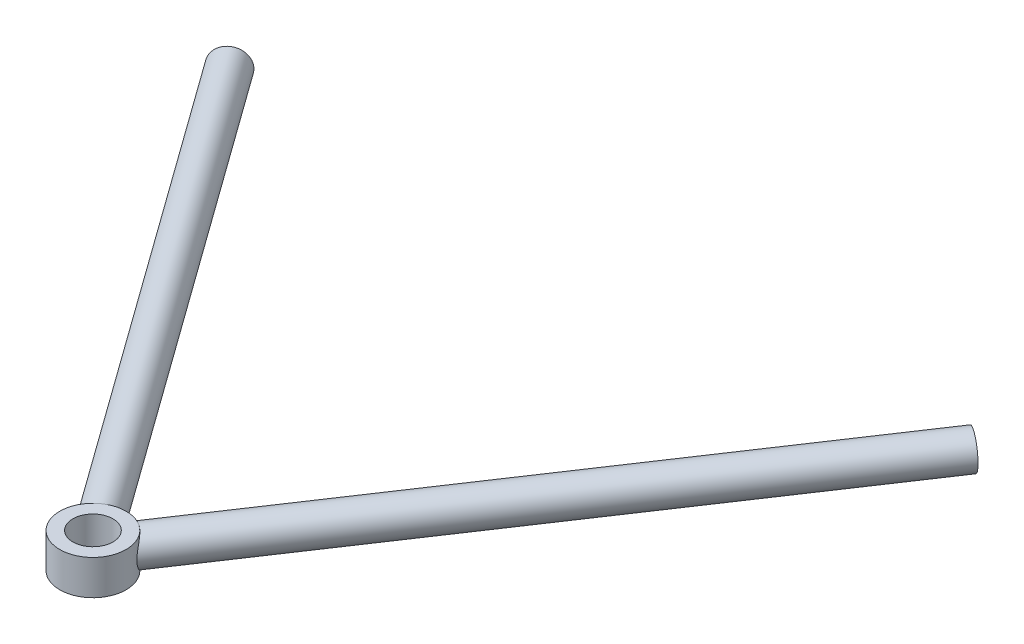
SolidWorks part; units mm, degrees
material "AISI 4130 Steel, annealed at 865C"
ref_plane "Front Plane" through (0, 0, 0) normal (0, 0, 1) x (1, 0, 0)
ref_plane "Top Plane" through (0, 0, 0) normal (0, 1, 0) x (1, 0, 0)
ref_plane "Right Plane" through (0, 0, 0) normal (1, 0, 0) x (0, 0, -1)
sketch "Sketch1" plane through (0, 0, 0) normal (0, 1, 0) x (1, 0, 0)
  circle A0 centre (0, 0) radius 11.5062
  circle A1 centre (0, 0) radius 19.0062
  dimension "D3" = 23.0124
  dimension "D1" = 38.0124
extrude "Boss-Extrude1" add sketch "Sketch1" along normal mid plane 20
sketch "Sketch3" plane through (0, 0, 0) normal (0, 1, 0) x (1, 0, 0)
  line L0 (-19.0062, 0) -> (19.0062, 0) construction
  line L1 (0, 0) -> (-219.5, 305.0017) construction
  line L2 (0, 0) -> (201.8849, 302.3522) construction
  line L3 (-11.102, 15.4266) -> (-219.5, 305.0017) construction
  line L4 (10.5542, 15.8065) -> (201.8849, 302.3522) construction
  line L6 (201.8849, 302.3522) -> (223.5693, 287.8732) construction
  line L7 (-200.9705, 279.2544) -> (-227.4729, 260.1815) construction
  line L8 (0, 0) -> (219.5, 328.7334) construction
  line L9 (-219.5, 305.0017) -> (219.5, 328.7334) construction
  circle A0 centre (0, 0) radius 19.0062 construction
  circle A1 centre (0, 0) radius 19.0062 construction
  dimension "D1" = 54.259
  dimension "D2" = 56.268
  dimension "D3" = 375.7743
  dimension "D5" = 31.7217
  dimension "D4" = 395.2795
  dimension "D6" = 31.7217
ref_plane "tube1plane" through (201.8849, 0, -302.3522) normal (0.5553, 0, -0.8316) x (0.8316, 0, 0.5553)
ref_plane "tube2plane" through (-200.9705, 0, -279.2544) normal (-0.5841, 0, -0.8117) x (-0.8117, 0, 0.5841)
sketch "Sketch5" plane through (201.8849, 0, -302.3522) normal (0.5553, 0, -0.8316) x (0.8316, 0, 0.5553)
  circle A0 centre (0, 0) radius 10
  circle A1 centre (0, 0) radius 7
  dimension "D1" = 20
  dimension "D2" = 14
extrude "Boss-Extrude2" add sketch "Sketch5" against normal up to next
sketch "Sketch6" plane through (-200.9705, 0, -279.2544) normal (-0.5841, 0, -0.8117) x (-0.8117, 0, 0.5841)
  circle A0 centre (0, 0) radius 10
  circle A1 centre (0, 0) radius 7
  dimension "D1" = 20
  dimension "D2" = 14
extrude "Boss-Extrude3" add sketch "Sketch6" against normal up to surface (327.8898 mm away) up to face at (4.4874, -0.3899, 2.7702)
equation "\"CA_ID\"= 14"
equation "\"D2@Sketch5\"=\"CA_ID\""
equation "\"D2@Sketch6\"=\"CA_ID\""
equation "\"tube_end_to_ball_center\" = 31.721675mm"
equation "\"D6@Sketch3\"=\"tube_end_to_ball_center\""
equation "\"D5@Sketch3\"=\"tube_end_to_ball_center\""
